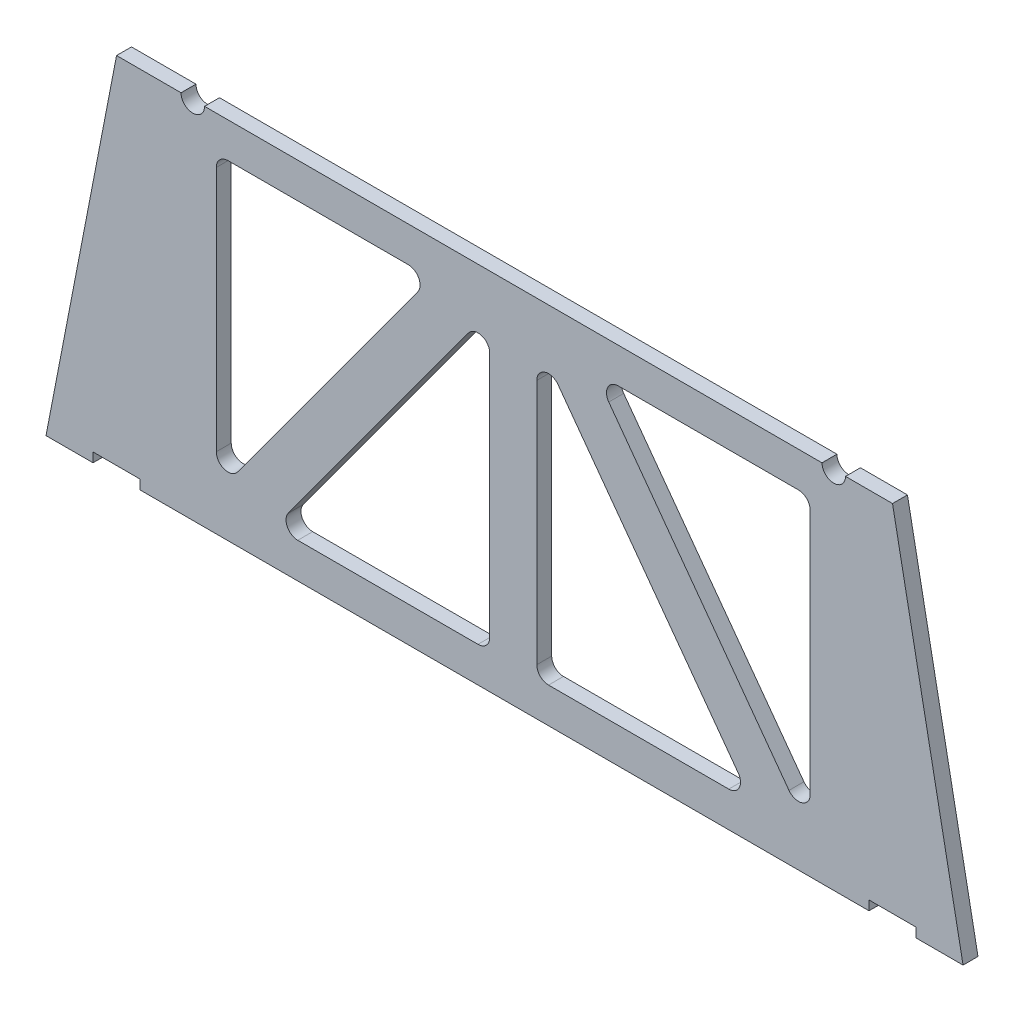
SolidWorks part; units mm, degrees
ref_plane "Front Plane" through (0, 0, 0) normal (0, 0, 1) x (1, 0, 0)
ref_plane "Top Plane" through (0, 0, 0) normal (0, 1, 0) x (1, 0, 0)
ref_plane "Right Plane" through (0, 0, 0) normal (1, 0, 0) x (0, 0, -1)
sketch "Sketch1" plane through (0, 0, 0) normal (0, 0, 1) x (1, 0, 0)
  line L0 (-158.7125, -77.5) -> (151.2875, -77.5)
  line L1 (191.2875, -77.5) -> (161.2875, 77.5)
  line L2 (161.2875, 77.5) -> (141.2875, 77.5)
  line L3 (-168.7125, 77.5) -> (-198.7125, -77.5)
  line L4 (-198.7125, -77.5) -> (-178.7125, -77.5)
  line L5 (-178.7125, -77.5) -> (-178.7125, -73.5)
  line L6 (-178.7125, -73.5) -> (-158.7125, -73.5)
  line L7 (-158.7125, -73.5) -> (-158.7125, -77.5)
  line L8 (-168.7125, 77.5) -> (-141.2875, 77.5)
  line L9 (151.2875, -77.5) -> (151.2875, -73.5)
  line L10 (151.2875, -73.5) -> (171.2875, -73.5)
  line L11 (171.2875, -73.5) -> (171.2875, -77.5)
  line L12 (171.2875, -77.5) -> (191.2875, -77.5)
  line L13 (-168.7125, 77.5) -> (-141.2875, 77.5)
  line L14 (0, -77.5) -> (0, 77.5) construction
  line L15 (-131.2875, 77.5) -> (131.2875, 77.5)
  line L16 (-126.2875, 57.5) -> (-126.2875, -47.2046)
  line L17 (-117.2529, -50.1579) -> (-40.6078, 54.5466)
  line L18 (-121.2875, 62.5) -> (-44.6424, 62.5)
  line L19 (-95.6797, -54.5466) -> (-19.0346, 50.1579)
  line L20 (-10, 47.2046) -> (-10, -57.5)
  line L21 (-91.6451, -62.5) -> (-15, -62.5)
  line L22 (15, -62.5) -> (91.6451, -62.5)
  line L23 (10, 47.2046) -> (10, -57.5)
  line L24 (95.6797, -54.5466) -> (19.0346, 50.1579)
  line L25 (44.6424, 62.5) -> (121.2875, 62.5)
  line L26 (117.2529, -50.1579) -> (40.6078, 54.5466)
  line L27 (126.2875, 57.5) -> (126.2875, -47.2046)
  arc A0 (-141.2875, 77.5) -> (-131.2875, 77.5) centre (-136.2875, 77.5) ccw
  arc A1 (141.2875, 77.5) -> (131.2875, 77.5) centre (136.2875, 77.5) cw
  arc A2 (-126.2875, 57.5) -> (-121.2875, 62.5) centre (-121.2875, 57.5) cw
  arc A3 (-117.2529, -50.1579) -> (-126.2875, -47.2046) centre (-121.2875, -47.2046) cw
  arc A4 (-40.6078, 54.5466) -> (-44.6424, 62.5) centre (-44.6424, 57.5) ccw
  arc A5 (-10, 47.2046) -> (-19.0346, 50.1579) centre (-15, 47.2046) ccw
  arc A6 (-15, -62.5) -> (-10, -57.5) centre (-15, -57.5) ccw
  arc A7 (-91.6451, -62.5) -> (-95.6797, -54.5466) centre (-91.6451, -57.5) cw
  arc A8 (10, 47.2046) -> (19.0346, 50.1579) centre (15, 47.2046) cw
  arc A9 (10, -57.5) -> (15, -62.5) centre (15, -57.5) ccw
  arc A10 (91.6451, -62.5) -> (95.6797, -54.5466) centre (91.6451, -57.5) ccw
  arc A11 (44.6424, 62.5) -> (40.6078, 54.5466) centre (44.6424, 57.5) ccw
  arc A12 (126.2875, 57.5) -> (121.2875, 62.5) centre (121.2875, 57.5) ccw
  arc A13 (117.2529, -50.1579) -> (126.2875, -47.2046) centre (121.2875, -47.2046) ccw
  point P15 (0, -77.5)
  point P29 (0, 0)
  point P37 (-126.2875, 62.5)
  point P40 (-126.2875, -62.5)
  point P43 (-34.7858, 62.5)
  point P46 (-10, 62.5)
  point P49 (-10, -62.5)
  point P52 (-101.5017, -62.5)
  point P55 (10, 62.5)
  point P58 (10, -62.5)
  point P61 (101.5017, -62.5)
  point P64 (34.7858, 62.5)
  point P67 (126.2875, 62.5)
  point P70 (126.2875, -62.5)
  dimension "D18" = 5
  dimension "D1" = 20
  dimension "D2" = 20
  dimension "D3" = 20
  dimension "D4" = 282.575
  dimension "D5" = 15
  dimension "D6" = 10
  dimension "D7" = 20
  dimension "D8" = 4
  dimension "D9" = 10
  dimension "D10" = 310
  dimension "D11" = 5
  dimension "D13" = 20
  dimension "D14" = 10
  dimension "D15" = 15
  dimension "D16" = 155
  dimension "D17" = 5
extrude "Extrude1" add sketch "Sketch1" along normal blind 6.35 contours L0 L14 L15 A0 L8 L3 L4 L5 L6 L7 L16 L18 L17 L21 L19 L20 | L14 L0 L9 L10 L11 L12 L1 L2 A1 L15 L25 L27 L26 L24 L22 L23 region at (-156.1923, -75.5, 0) region at (2.462, 0, 0)
